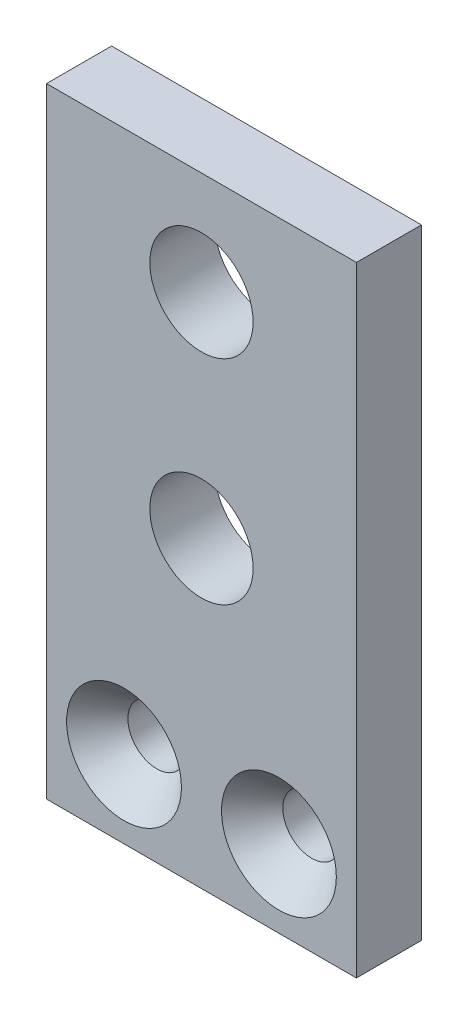
SolidWorks part; units mm, degrees
ref_plane "Front Plane" through (0, 0, 0) normal (0, 0, 1) x (1, 0, 0)
ref_plane "Top Plane" through (0, 0, 0) normal (0, 1, 0) x (1, 0, 0)
ref_plane "Right Plane" through (0, 0, 0) normal (1, 0, 0) x (0, 0, -1)
sketch "Sketch1" plane through (0, 0, 0) normal (0, 0, 1) x (1, 0, 0)
  line L1 (-4.7625, -9.525) -> (4.7625, -9.525)
  line L2 (-4.7625, -9.525) -> (-4.7625, 9.525)
  line L3 (-4.7625, 9.525) -> (4.7625, 9.525)
  line L4 (4.7625, -9.525) -> (4.7625, 9.525)
  line L5 (-4.7625, -9.525) -> (4.7625, 9.525) construction
  line L6 (-4.7625, 9.525) -> (4.7625, -9.525) construction
  point P0 (0, 0)
  dimension "D1" = 9.525
  dimension "D2" = 19.05
extrude "Boss-Extrude1" add sketch "Sketch1" along normal blind 2
hole_wizard "CSK for #0 Flat Head Machine Screw (100)1" positions "Sketch3" profile "Sketch2" countersink size "#0" standard "Ansi Inch" end condition through all
sketch "Sketch3" plane through (0, 0, 2) normal (0, 0, 1) x (1, 0, 0)
  line L0 (-4.7625, 9.525) -> (-4.7625, -9.525) construction
  line L2 (-4.7625, -9.525) -> (4.7625, -9.525) construction
  line L3 (4.7625, -9.525) -> (4.7625, 9.525) construction
  point P0 (-2.3813, -7.1438)
  point P1 (2.3812, -7.1438)
  dimension "D1" = 2.3813
  dimension "D2" = 2.3813
  dimension "D3" = 2.3813
sketch "Sketch2" plane through (-2.3813, -7.1438, 2) normal (1, 0, 0) x (0, -1, 0)
  line L0 (0, 0) -> (0, 2)
  line L1 (0, 2) -> (0.889, 2)
  line L2 (0.889, 2) -> (0.889, 1.0081)
  line L3 (0.889, 1.0081) -> (1.7653, 0)
  line L5 (1.7653, 0) -> (0, 0)
  line L6 (-0.889, 1.0081) -> (-1.7653, 0) construction
  line L11 (0, -6.35) -> (0, 107.95) construction
  dimension "Thru Hole Dia." = 1.778
  dimension "Thru Hole Depth" = 2
  dimension "Near C'Sink Dia." = 3.5306
  dimension "Near C'Sink Angle" = 82
hole_wizard "1/8 (0.125) Diameter Hole1" positions "Sketch5" profile "Sketch4" hole size "1/8" standard "Ansi Inch"
sketch "Sketch5" plane through (0, 0, 2) normal (0, 0, 1) x (1, 0, 0)
  line L0 (4.7625, 9.525) -> (-4.7625, 9.525) construction
  point P0 (0, 6.35)
  point P1 (0, -0.2032)
  point P8 (0, 9.525)
  dimension "D1" = 3.175
  dimension "D2" = 6.5532
sketch "Sketch4" plane through (0, 6.35, 2) normal (1, 0, 0) x (0, -1, 0)
  line L0 (0, 0) -> (0, 5.0179)
  line L1 (0, 5.0179) -> (1.5875, 4.064)
  line L2 (1.5875, 4.064) -> (1.5875, 0)
  line L5 (1.5875, 0) -> (0, 0)
  line L10 (0, 5.0179) -> (-1.5875, 4.064) construction
  line L11 (0, -6.35) -> (0, 107.95) construction
  dimension "Hole Dia." = 3.175
  dimension "Hole Depth" = 4.064
  dimension "Drill Angle" = 118
